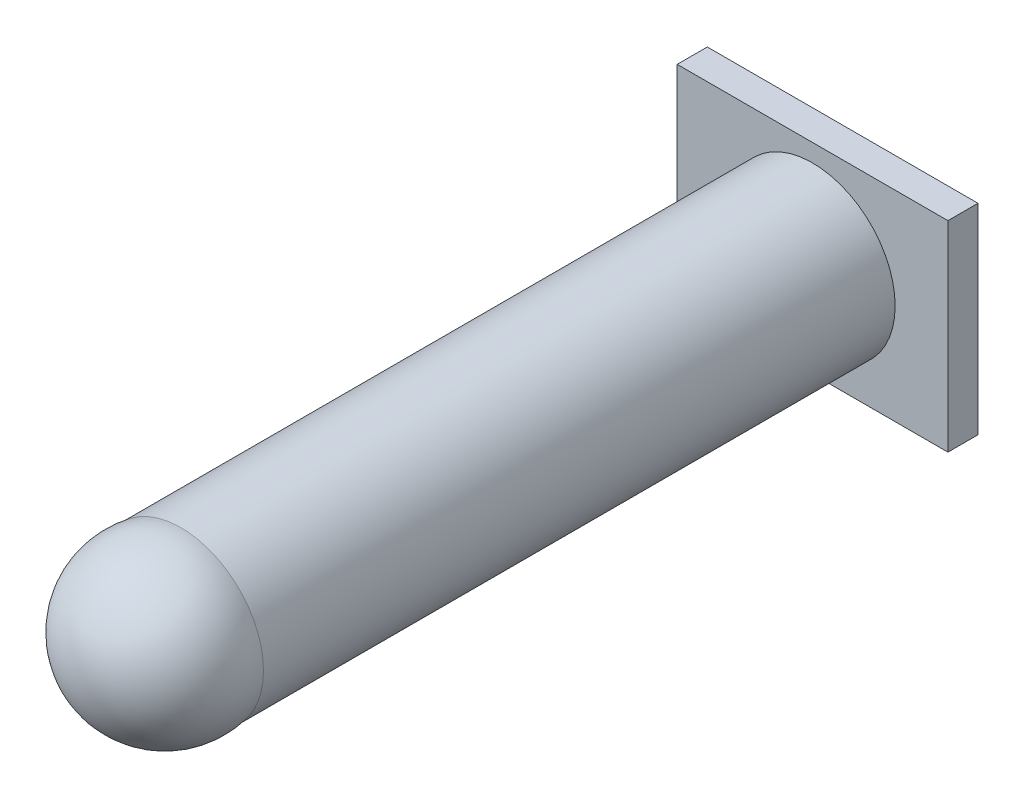
SolidWorks part; units mm, degrees
ref_plane "Plan de face" through (0, 0, 0) normal (0, 0, 1) x (1, 0, 0)
ref_plane "Plan de dessus" through (0, 0, 0) normal (0, 1, 0) x (1, 0, 0)
ref_plane "Plan de droite" through (0, 0, 0) normal (1, 0, 0) x (0, 0, -1)
sketch "Esquisse1" plane through (0, 0, 0) normal (0, 0, 1) x (1, 0, 0)
  line L1 (-45.5198, 26.1199) -> (-18.5198, 26.1199)
  line L2 (-45.5198, 26.1199) -> (-45.5198, 6.1199)
  line L3 (-45.5198, 6.1199) -> (-18.5198, 6.1199)
  line L4 (-18.5198, 26.1199) -> (-18.5198, 6.1199)
  dimension "D1" = 27
  dimension "D2" = 20
extrude "Boss.-Extru.1" add sketch "Esquisse1" along normal blind 3
sketch "Esquisse2" plane through (0, 0, 3) normal (0, 0, 1) x (1, 0, 0)
  line L0 (-18.5198, 26.1199) -> (-45.5198, 26.1199) construction
  line L1 (-45.5198, 26.1199) -> (-45.5198, 6.1199) construction
  circle A0 centre (-32.0198, 16.1199) radius 8.2365
  dimension "D1" = 10
  dimension "D2" = 13.5
extrude "Boss.-Extru.2" add sketch "Esquisse2" along normal blind 63
dome "Dôme1" faces to dome 1 distance 10 reverse direction no elliptical dome no face at (-23.7833, 16.1199, 66) parameters "D1"=10
